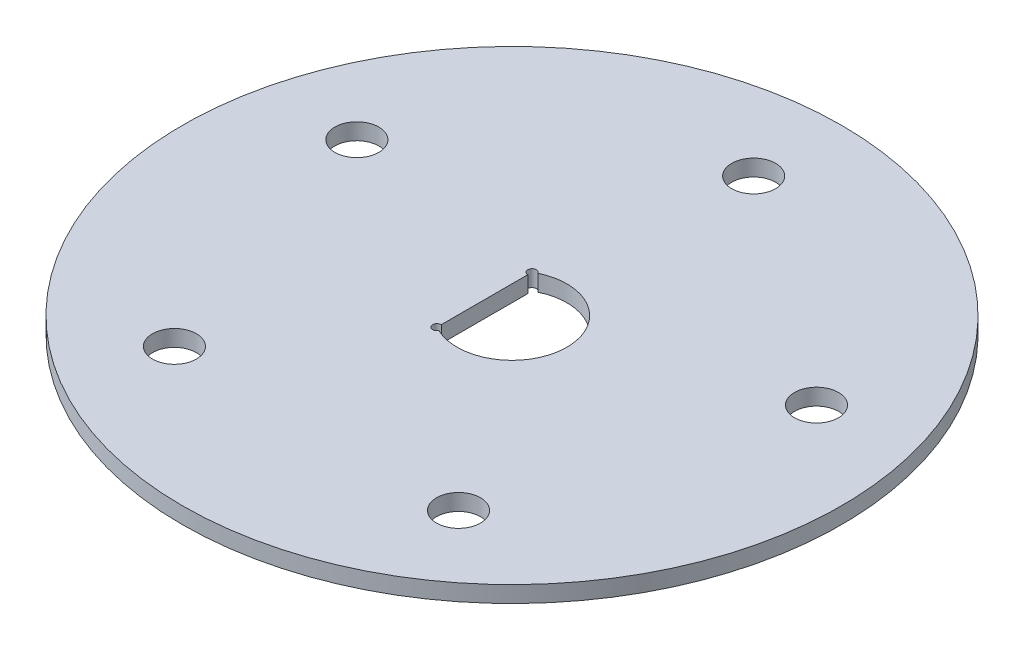
SolidWorks part; units mm, degrees
ref_plane "Front Plane" through (0, 0, 0) normal (0, 0, 1) x (1, 0, 0)
ref_plane "Top Plane" through (0, 0, 0) normal (0, 1, 0) x (1, 0, 0)
ref_plane "Right Plane" through (0, 0, 0) normal (1, 0, 0) x (0, 0, -1)
sketch "Sketch1" plane through (0, 0, 0) normal (0, 1, 0) x (1, 0, 0)
  line L2 (-3.175, 5.4993) -> (-3.175, -5.4993)
  circle A0 centre (0, 0) radius 38.1
  circle A2 centre (0, 27.94) radius 2.54
  circle A9 centre (26.5725, 8.6339) radius 2.54
  circle A10 centre (16.4227, -22.6039) radius 2.54
  circle A11 centre (-16.4227, -22.6039) radius 2.54
  circle A12 centre (-26.5725, 8.6339) radius 2.54
  arc A13 (-3.175, -5.4993) -> (-3.175, 5.4993) centre (0, 0) ccw
  point P18 (0, 0)
  point P19 (0, 0)
  dimension "D1" = 76.2
  dimension "D2" = 12.7
  dimension "D3" = 5.08
  dimension "D6" = 3.175
  dimension "D4" = 27.94
  dimension "D5" = 5
extrude "Boss-Extrude1" add sketch "Sketch1" along normal blind 1.8974 contours A0 | A12 | A11 | A10 | A9 | A13 L2 | A2
sketch "Sketch2" plane through (0, 1.8974, 0) normal (0, 1, 0) x (1, 0, 0)
  circle A0 centre (-3.175, 5.4993) radius 0.5
  circle A1 centre (-3.175, -5.4993) radius 0.5
  dimension "D1" = 1
extrude "Cut-Extrude1" cut sketch "Sketch2" against normal through all both and the other way through all
